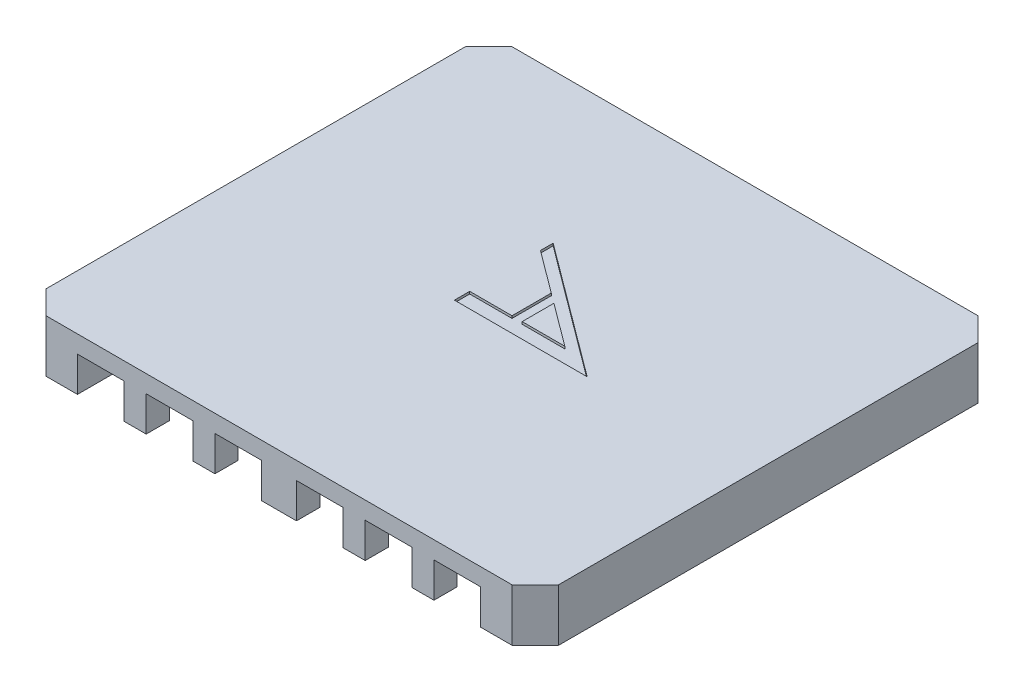
SolidWorks part; units mm, degrees
ref_plane "前视基准面" through (0, 0, 0) normal (0, 0, 1) x (1, 0, 0)
ref_plane "上视基准面" through (0, 0, 0) normal (0, 1, 0) x (1, 0, 0)
ref_plane "右视基准面" through (0, 0, 0) normal (1, 0, 0) x (0, 0, -1)
sketch "草图1" plane through (0, 0, 0) normal (0, 1, 0) x (1, 0, 0)
  line L0 (-38.5609, 0) -> (35.1038, 0) construction
  line L1 (0, 61.5645) -> (0, -41.0874) construction
  line L3 (-22, 20) -> (22, 20)
  line L4 (-22, 20) -> (-22, -20)
  line L5 (-22, -20) -> (22, -20)
  line L6 (22, 20) -> (22, -20)
  line L7 (-22, 20) -> (22, -20) construction
  line L8 (-22, -20) -> (22, 20) construction
  point P5 (0, 0)
  dimension "D1" = 44
  dimension "D2" = 40
extrude "凸台-拉伸1" add sketch "草图1" along normal blind 4.5
chamfer "倒角1" distance 2 angle 45 4 edges at (-22, 2.25, -20) (22, 2.25, -20) (22, 2.25, 20) (-22, 2.25, 20)
sketch "草图2" plane through (0, 0, 0) normal (0, -1, 0) x (1, 0, 0)
  line L0 (-26.6072, 0) -> (29.6093, 0) construction
  line L1 (0, 21.5153) -> (0, -22.2217) construction
  line L4 (-20, 18) -> (20, 18)
  line L5 (-17.3, 18) -> (17.3, 18)
  line L6 (-1.5, 10) -> (-1.5, -10)
  line L7 (20, -18) -> (-20, -18)
  line L8 (17.3, -18) -> (-17.3, -18)
  line L9 (1.5, 10) -> (1.5, -10)
  line L10 (-17.3, 18) -> (-17.3, -18)
  line L11 (17.3, 18) -> (17.3, -18)
  line L12 (-1.5, 10) -> (1.5, 10)
  line L13 (-1.5, -10) -> (1.5, -10)
  line L14 (-26.6072, 10) -> (29.6093, 10) construction
  line L15 (-26.6072, -10) -> (29.6093, -10) construction
  line L16 (-17.3, 21.5153) -> (-17.3, -22.2217) construction
  line L17 (17.3, 21.5153) -> (17.3, -22.2217) construction
  line L18 (1.5, 21.5153) -> (1.5, -22.2217) construction
  line L19 (-1.5, 21.5153) -> (-1.5, -22.2217) construction
  dimension "D1" = 2
  dimension "D2" = 2
  dimension "D3" = 1.5
  dimension "D4" = 1.5
  dimension "D5" = 15.8
  dimension "D6" = 15.8
  dimension "D7" = 10
  dimension "D8" = 10
extrude "切除-拉伸1" cut sketch "草图2" against normal blind 3
sketch "草图3" plane through (0, 0, 0) normal (0, -1, 0) x (1, 0, 0)
  line L0 (-31.8657, 0) -> (28.4725, 0) construction
  line L1 (0, 25.2743) -> (0, -28.2052) construction
  line L2 (-20, 20) -> (20, 20) construction
  line L3 (-17.3, -18) -> (17.3, -18) construction
  line L4 (-17.3, 20) -> (-13.3, 20)
  line L5 (17.3, 18) -> (-17.3, 18) construction
  line L6 (-1.5, 20) -> (-1.5, 18)
  line L7 (-5.5, 20) -> (-5.5, 18)
  line L8 (-7.4, 20) -> (-7.4, 18)
  line L9 (-11.4, 20) -> (-11.4, 18)
  line L10 (-13.3, 20) -> (-13.3, 18)
  line L11 (-17.3, 18) -> (-17.3, -18) construction
  line L13 (-11.4, 20) -> (-7.4, 20)
  line L14 (-13.3, 18) -> (-17.3, 18)
  line L15 (-5.5, 20) -> (-1.5, 20)
  line L16 (-7.4, 18) -> (-11.4, 18)
  line L17 (1.5, 18) -> (5.5, 18)
  line L18 (-1.5, 18) -> (-5.5, 18)
  line L19 (-1.5, 25.2743) -> (-1.5, -28.2052) construction
  line L20 (-5.5, 25.2743) -> (-5.5, -28.2052) construction
  line L21 (-7.4, 25.2743) -> (-7.4, -28.2052) construction
  line L22 (-11.4, 25.2743) -> (-11.4, -28.2052) construction
  line L23 (-13.3, 25.2743) -> (-13.3, -28.2052) construction
  line L24 (7.4, 18) -> (11.4, 18)
  line L25 (5.5, 20) -> (1.5, 20)
  line L26 (13.3, 18) -> (17.3, 18)
  line L27 (11.4, 20) -> (7.4, 20)
  line L28 (13.3, 20) -> (13.3, 18)
  line L29 (11.4, 20) -> (11.4, 18)
  line L30 (7.4, 20) -> (7.4, 18)
  line L31 (5.5, 20) -> (5.5, 18)
  line L32 (1.5, 20) -> (1.5, 18)
  line L33 (17.3, 20) -> (13.3, 20)
  line L34 (-17.3, 20) -> (-17.3, 18)
  line L35 (17.3, 20) -> (17.3, 18)
  line L37 (-3.7, -18) -> (-1.5, -18)
  line L38 (-3.7, -18) -> (-3.7, -20)
  line L39 (-3.7, -20) -> (-1.5, -20)
  line L40 (-1.5, -18) -> (-1.5, -20)
  line L41 (20, -20) -> (-20, -20) construction
  line L42 (-17.3, -18) -> (17.3, -18) construction
  line L43 (-10.65, -18) -> (-8.15, -18)
  line L44 (-10.65, -18) -> (-10.65, -20)
  line L45 (-10.65, -20) -> (-8.15, -20)
  line L46 (-8.15, -18) -> (-8.15, -20)
  line L47 (-17.3, 18) -> (-17.3, -18) construction
  line L48 (-17.3, -18) -> (-15.1, -18)
  line L49 (-17.3, -18) -> (-17.3, -20)
  line L50 (-17.3, -20) -> (-15.1, -20)
  line L51 (-15.1, -18) -> (-15.1, -20)
  line L52 (15.1, -18) -> (15.1, -20)
  line L53 (17.3, -20) -> (15.1, -20)
  line L54 (17.3, -18) -> (17.3, -20)
  line L55 (17.3, -18) -> (15.1, -18)
  line L56 (8.15, -18) -> (8.15, -20)
  line L57 (10.65, -20) -> (8.15, -20)
  line L58 (10.65, -18) -> (10.65, -20)
  line L59 (10.65, -18) -> (8.15, -18)
  line L60 (1.5, -18) -> (1.5, -20)
  line L61 (3.7, -20) -> (1.5, -20)
  line L62 (3.7, -18) -> (3.7, -20)
  line L63 (3.7, -18) -> (1.5, -18)
  dimension "D6" = 2.2
  dimension "D7" = 1.5
  dimension "D8" = 2.5
  dimension "D9" = 2.2
  dimension "D10" = 8.15
  dimension "D1" = 1.5
  dimension "D2" = 5.5
  dimension "D3" = 7.4
  dimension "D4" = 11.4
  dimension "D5" = 13.3
extrude "切除-拉伸2" cut sketch "草图3" against normal blind 3
sketch "草图4" plane through (0, 0, 0) normal (0, -1, 0) x (1, 0, 0)
  line L0 (22, 18) -> (22, -18) construction
  line L1 (-22, -18) -> (-22, 18) construction
  circle A0 centre (19.3, 15) radius 1
  circle A1 centre (19.3, -12) radius 1
  circle A2 centre (-19.3, 15) radius 1
  circle A3 centre (-19.3, -12) radius 1
  dimension "D5" = 2
  dimension "D1" = 15
  dimension "D2" = 12
  dimension "D3" = 2.7
  dimension "D4" = 2.7
extrude "切除-拉伸3" cut sketch "草图4" against normal blind 3.5
sketch "Sketch1" plane through (0, 4.5, 0) normal (0, 1, 0) x (1, 0, 0)
  line L0 (0.8719, 0) -> (4.5348, 0)
  line L1 (6, 0) -> (-3.6292, 7.1609) construction
  line L2 (-3.6292, 7.1609) -> (-3.6292, 0) construction
  line L3 (-3.6292, 0) -> (0, 0)
  line L4 (4.5348, 0) -> (0.8719, 2.724)
  line L5 (-3.6292, 7.1609) -> (6, 0)
  line L6 (6, 0) -> (7.7645, -1.3122)
  line L8 (-3.6292, -1.3122) -> (-3.6292, 0)
  line L9 (-3.6292, 7.1609) -> (-3.6292, 6.0713)
  line L10 (0, 0) -> (0, 3.3724)
  line L11 (0.8719, 0) -> (0.8719, 2.724)
  line L12 (0, 3.3724) -> (-3.6292, 6.0713)
  line L13 (7.7645, -1.3122) -> (-3.6292, -1.3122)
extrude "Cut-Extrude1" cut sketch "Sketch1" against normal blind 0.2
